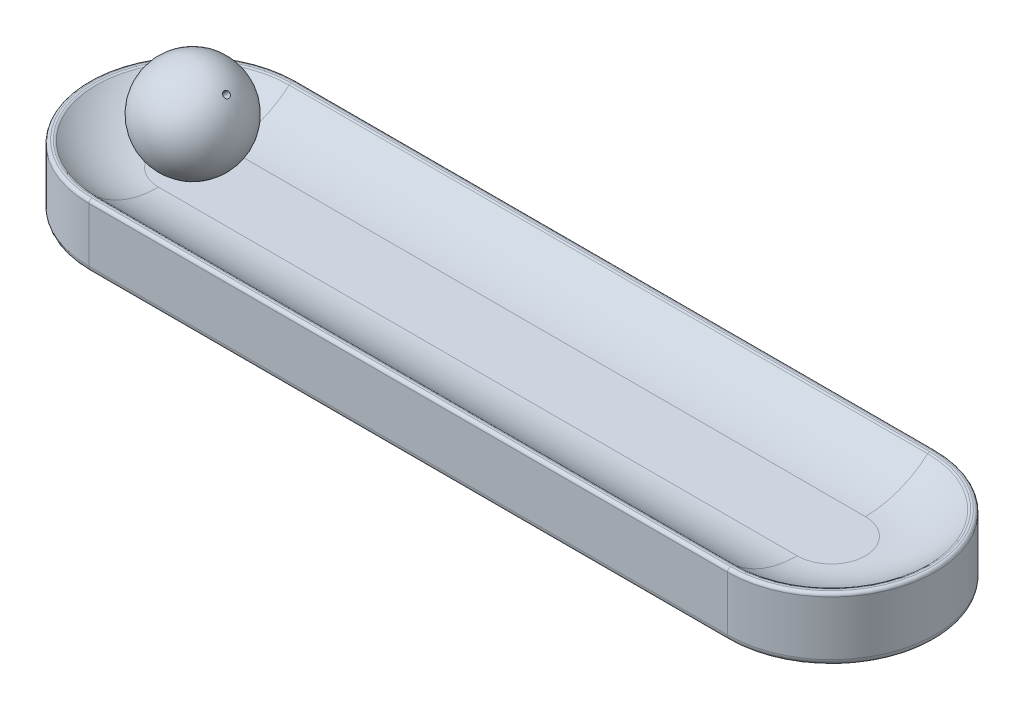
SolidWorks part; units mm, degrees
ref_plane "Front Plane" through (0, 0, 0) normal (0, 0, 1) x (1, 0, 0)
ref_plane "Top Plane" through (0, 0, 0) normal (0, 1, 0) x (1, 0, 0)
ref_plane "Right Plane" through (0, 0, 0) normal (1, 0, 0) x (0, 0, -1)
sketch "Sketch1" plane through (0, 0, 0) normal (0, 1, 0) x (1, 0, 0)
  line L0 (-100, 0) -> (100, 0) construction
  line L1 (-100, 32.5) -> (100, 32.5)
  line L2 (-100, -32.5) -> (100, -32.5)
  arc A0 (-100, 32.5) -> (-100, -32.5) centre (-100, 0) ccw
  arc A1 (100, -32.5) -> (100, 32.5) centre (100, 0) ccw
  point P3 (0, 0)
  dimension "D1" = 200
  dimension "D2" = 65
extrude "Boss-Extrude1" add sketch "Sketch1" along normal blind 20
sketch "Sketch2" plane through (0, 20, 0) normal (0, 1, 0) x (1, 0, 0)
  line L4 (-100, -30.5) -> (100, -30.5)
  line L5 (100, 30.5) -> (-100, 30.5)
  line L6 (-100, -30.5) -> (100, -30.5)
  line L7 (100, 30.5) -> (-100, 30.5)
  arc A4 (-100, 30.5) -> (-100, -30.5) centre (-100, 0) ccw
  arc A5 (100, -30.5) -> (100, 30.5) centre (100, 0) ccw
  arc A6 (-100, 30.5) -> (-100, -30.5) centre (-100, 0) ccw
  arc A7 (100, -30.5) -> (100, 30.5) centre (100, 0) ccw
  dimension "D1" = 2
extrude "Cut-Extrude1" cut sketch "Sketch2" against normal blind 7.5
fillet "Fillet1" radius 30 4 edges at (0, 12.5, -30.5) (0, 12.5, 30.5) (-130.5, 12.5, 0) (130.5, 12.5, 0)
fillet "Fillet2" radius 1 8 edges at (0, 20, -30.5) (0, 20, 30.5) (0, 20, -32.5) (132.5, 20, 0) (0, 20, 32.5) (-132.5, 20, 0) (-130.5, 20, 0) (130.5, 20, 0)
fillet "Fillet3" radius 2 4 edges at (0, 0, 32.5) (132.5, 0, 0) (0, 0, -32.5) (-132.5, 0, 0)
sketch "Sketch4" plane through (0, 0, 0) normal (0, 0, 1) x (1, 0, 0)
  line L0 (-100, 12) -> (-100, 42) construction
  line L1 (-100, 19) -> (-100, 2) construction
  line L2 (100, 12.5) -> (-100, 12.5) construction
  line L3 (-100, 12) -> (-100, 42)
  arc A0 (-100, 42) -> (-100, 12) centre (-100, 27) ccw
  point P4 (-150, 11.2673)
  dimension "D3" = 15
  dimension "D1" = 30
  dimension "D2" = 0.5
revolve "Revolve1" add sketch "Sketch4" angle 360 about L0
sketch "Sketch5" plane through (0, 0, 0) normal (0, 0, 1) x (1, 0, 0)
  line L0 (-100, 27) -> (90.9188, 217.9188) construction
  line L1 (-100, 27) -> (-100, 42) construction
  line L2 (-100, 20) -> (100, 20) construction
  arc A0 (-96.1594, 12.5) -> (-103.8406, 12.5) centre (-100, 27) ccw construction
  point P8 (0, 0)
  dimension "D1" = 15
  dimension "D2" = 45
  dimension "D3" = 270
ref_plane "Plane1" through (-25.8934, -25.8934, 0) normal (0.7071, 0.7071, 0) x (0.7071, -0.7071, 0)
sketch "Sketch6" plane through (-25.8934, -25.8934, 0) normal (0.7071, 0.7071, 0) x (0.7071, -0.7071, 0)
  line L0 (-89.8026, 0) -> (-100.4092, 0) construction
  circle A0 centre (-89.8026, 0) radius 1
  point P4 (-124.1018, 0)
  dimension "D1" = 2
extrude "Cut-Extrude2" cut sketch "Sketch6" against normal up to vertex (15 mm away) up to point (-100, 27, 0)
